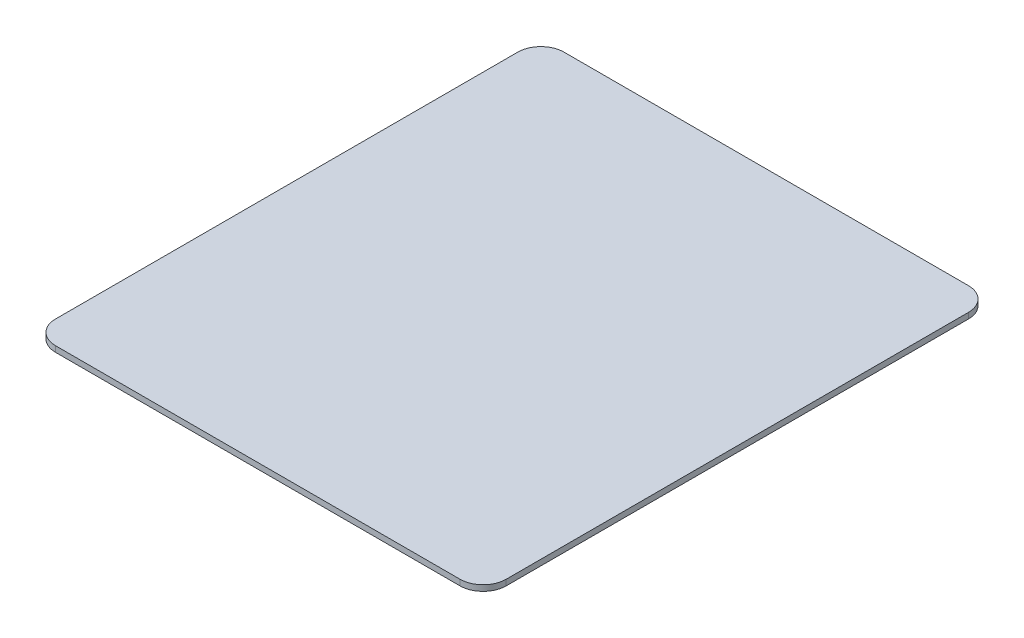
SolidWorks part; units mm, degrees
material "Acrylic (Medium-high impact)"
ref_plane "Front Plane" through (0, 0, 0) normal (0, 0, 1) x (1, 0, 0)
ref_plane "Top Plane" through (0, 0, 0) normal (0, 1, 0) x (1, 0, 0)
ref_plane "Right Plane" through (0, 0, 0) normal (1, 0, 0) x (0, 0, -1)
sketch "Sketch1" plane through (0, 0, 0) normal (0, 1, 0) x (1, 0, 0)
  line L1 (25, -31.5) -> (-25, -31.5)
  line L2 (25, -31.5) -> (25, 31.5)
  line L3 (25, 31.5) -> (-25, 31.5)
  line L4 (-25, -31.5) -> (-25, 31.5)
  line L5 (25, -31.5) -> (-25, 31.5) construction
  line L6 (25, 31.5) -> (-25, -31.5) construction
  line L7 (23, -29.5) -> (-23, -29.5)
  line L8 (23, -29.5) -> (23, 29.5)
  line L9 (23, 29.5) -> (-23, 29.5)
  line L10 (-23, -29.5) -> (-23, 29.5)
  line L11 (23, -29.5) -> (-23, 29.5) construction
  line L12 (23, 29.5) -> (-23, -29.5) construction
  point P0 (0, 0)
  point P6 (0, 0)
  dimension "D1" = 50
  dimension "D2" = 63
  dimension "D3" = 2
  dimension "D4" = 2
sketch "Sketch3" plane through (0, 0, 0) normal (0, 1, 0) x (1, 0, 0)
  line L0 (17.5, -22) -> (-17.5, -22)
  line L5 (19.5, -20) -> (19.5, 20)
  line L7 (17.5, 22) -> (-17.5, 22)
  line L8 (-19.5, -20) -> (-19.5, 20)
  line L9 (19.5, -22) -> (-19.5, 22) construction
  line L11 (19.5, 22) -> (-19.5, -22) construction
  arc A11 (-17.5, -22) -> (-19.5, -20) centre (-17.5, -20) cw
  arc A12 (17.5, -22) -> (19.5, -20) centre (17.5, -20) ccw
  arc A13 (19.5, 20) -> (17.5, 22) centre (17.5, 20) ccw
  arc A14 (-17.5, 22) -> (-19.5, 20) centre (-17.5, 20) ccw
  point P0 (0, 0)
  point P18 (0, 0)
  dimension "D2" = 39
  dimension "D1" = 2
  dimension "D3" = 44
extrude "Boss-Extrude1" add sketch "Sketch3" along normal blind 0.5 contours L7 A14 L8 A11 L0 A12 L5 A13 region at (0, 0, 0)
